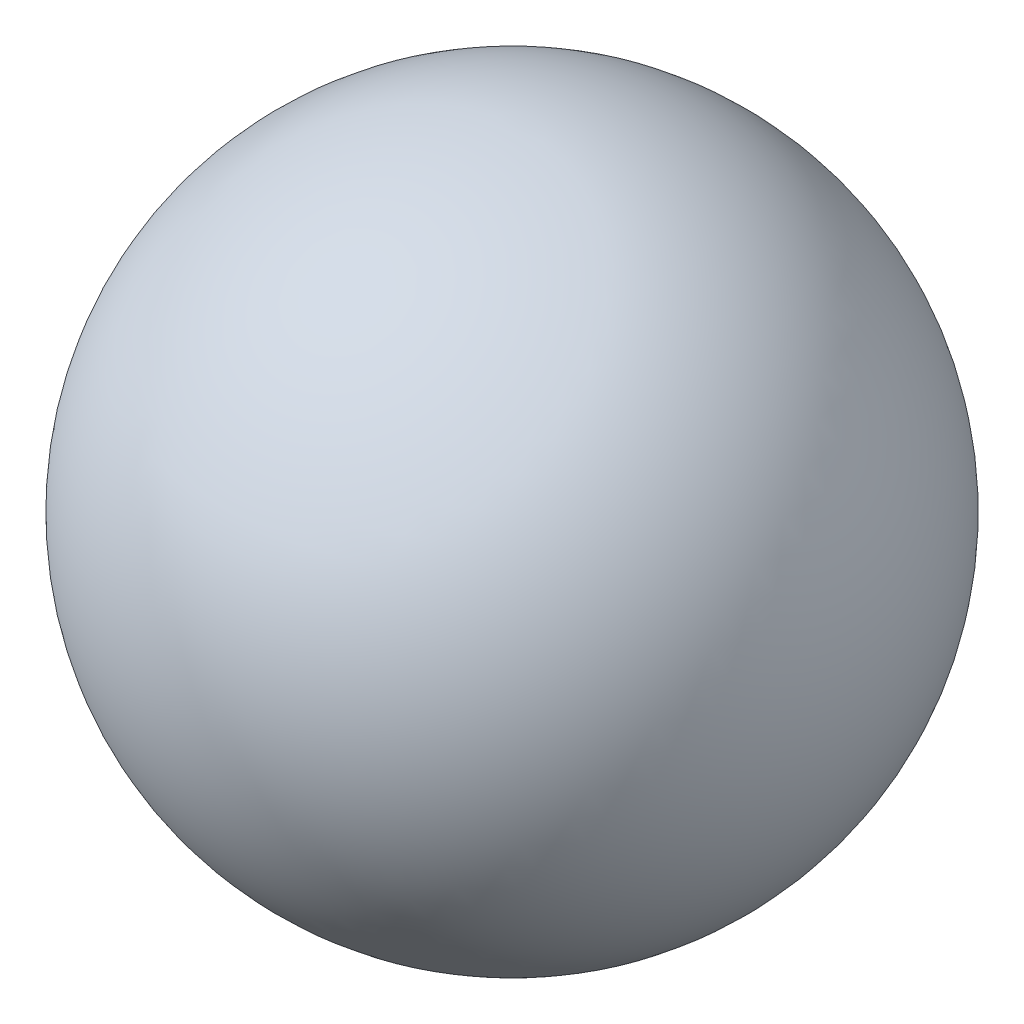
SolidWorks part; units mm, degrees
ref_plane "前视基准面" through (0, 0, 0) normal (0, 0, 1) x (1, 0, 0)
ref_plane "上视基准面" through (0, 0, 0) normal (0, 1, 0) x (1, 0, 0)
ref_plane "右视基准面" through (0, 0, 0) normal (1, 0, 0) x (0, 0, -1)
sketch "草图1" plane through (0, 0, 0) normal (0, 0, 1) x (1, 0, 0)
  line L0 (0, 17.311) -> (0, -16.7431) construction
  line L1 (0, 30) -> (0, -30)
  arc A0 (0, -30) -> (0, 30) centre (0, 0) ccw
  dimension "D1" = 60
revolve "旋转3" add sketch "草图1" angle 360 about L0
